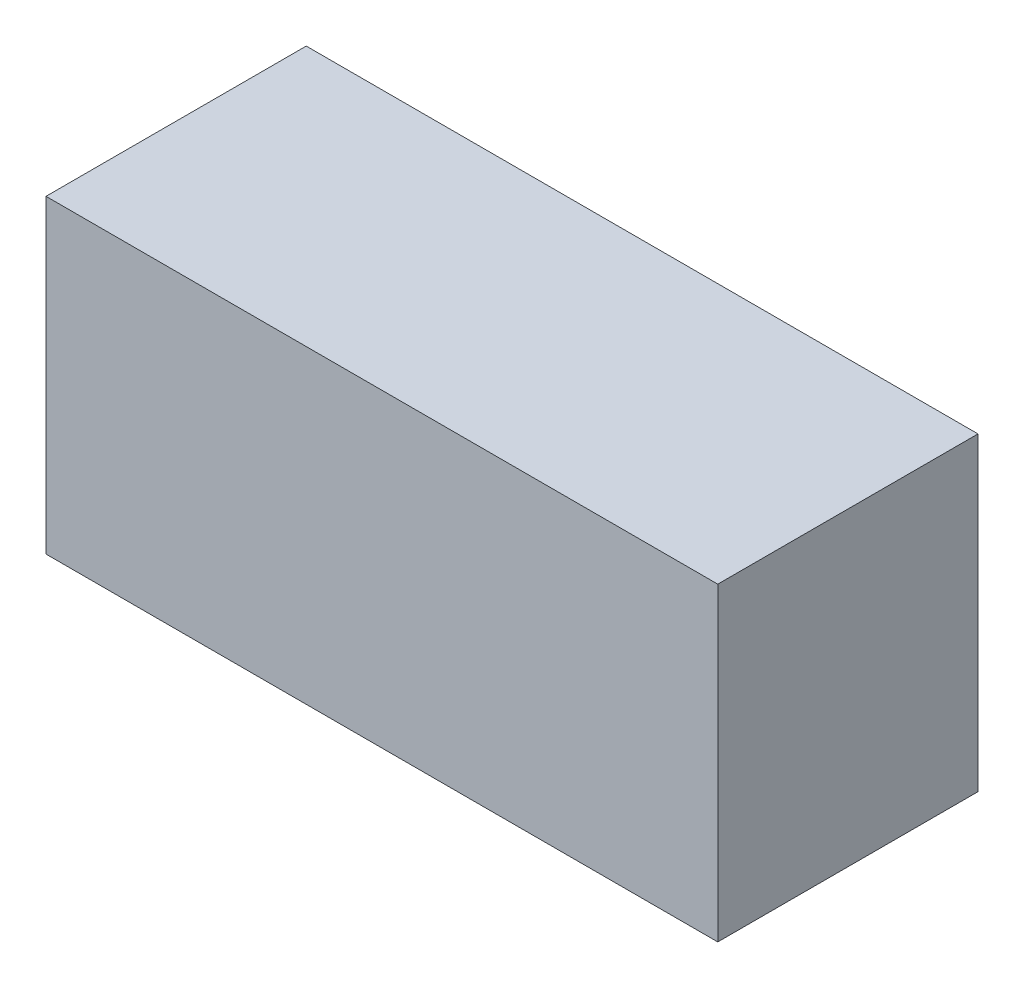
SolidWorks part; units mm, degrees
ref_plane "Front Plane" through (0, 0, 0) normal (0, 0, 1) x (1, 0, 0)
ref_plane "Top Plane" through (0, 0, 0) normal (0, 1, 0) x (1, 0, 0)
ref_plane "Right Plane" through (0, 0, 0) normal (1, 0, 0) x (0, 0, -1)
sketch "Sketch1" plane through (0, 0, 0) normal (0, 0, 1) x (1, 0, 0)
  line L1 (27.75, 12.8) -> (-27.75, 12.8)
  line L2 (27.75, 12.8) -> (27.75, -12.8)
  line L3 (27.75, -12.8) -> (-27.75, -12.8)
  line L4 (-27.75, 12.8) -> (-27.75, -12.8)
  line L5 (0, -12.8) -> (0, 12.8) construction
  line L6 (27.75, 0) -> (-27.75, 0) construction
  line L7 (-19.75, 10) -> (-24.75, 10)
  line L8 (-19.75, 10) -> (-19.75, -10)
  line L9 (-19.75, -10) -> (-24.75, -10)
  line L10 (-24.75, 10) -> (-24.75, -10)
  line L11 (-22.25, -10) -> (-22.25, 10) construction
  line L12 (-19.75, 0) -> (-24.75, 0) construction
  circle A0 centre (15.75, 0) radius 10
  point P0 (0, 0)
  point P4 (-22.25, 0)
  dimension "D3" = 20
  dimension "D7" = 12
  dimension "D1" = 55.5
  dimension "D2" = 25.6
  dimension "D4" = 20
  dimension "D5" = 5
  dimension "D6" = 3
extrude "Boss-Extrude1" add sketch "Sketch1" along normal blind 21.5
extrude "Boss-Extrude2" add sketch "Sketch1<2>" against normal offset from surface (18.5 mm away) 3 from surface contours L7 L10 L9 L8 | A0 region at (-22.25, 0, 0) region at (15.75, 0, 0) up to face at (-22.25, 0, 0) starting at face at (0, 0, 21.5)
sketch "Sketch1<2>" plane through (0, 0, 0) normal (0, 0, 1) x (1, 0, 0) same geometry as "Sketch1"
